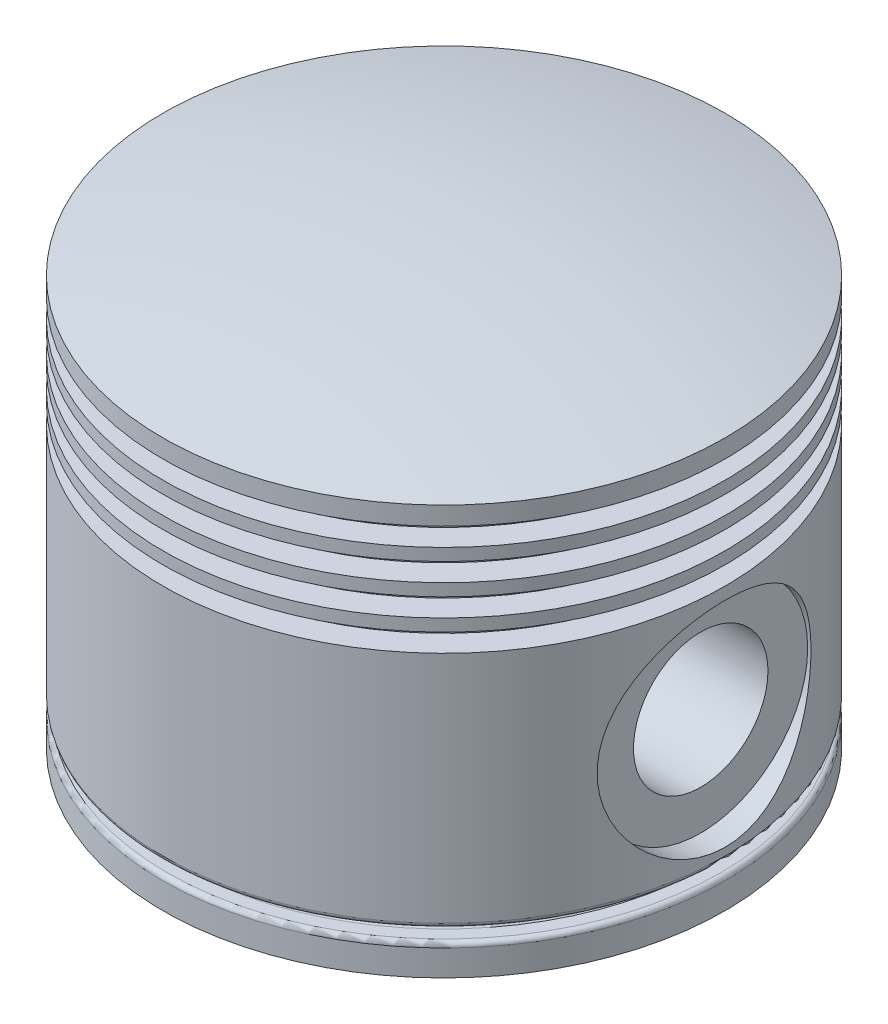
SolidWorks part; units mm, degrees
ref_plane "Front Plane" through (0, 0, 0) normal (0, 0, 1) x (1, 0, 0)
ref_plane "Top Plane" through (0, 0, 0) normal (0, 1, 0) x (1, 0, 0)
ref_plane "Right Plane" through (0, 0, 0) normal (1, 0, 0) x (0, 0, -1)
sketch "Sketch1" plane through (0, 0, 0) normal (0, 0, 1) x (1, 0, 0)
  line L0 (0, 0) -> (0, 81299.3192) construction
  line L1 (0, 0) -> (81299.3192, 0) construction
  line L2 (0, 72.6833) -> (0, 62)
  line L3 (0, 62) -> (37, 62)
  line L4 (37, 62) -> (37, 0)
  line L9 (37, 0) -> (46, 0)
  line L10 (46, 0) -> (46, 5)
  line L11 (46, 5) -> (42.5, 5)
  line L12 (42.5, 5) -> (42.5, 7)
  line L13 (42.5, 7) -> (46, 7)
  line L18 (46, 7) -> (46, 46)
  line L19 (46, 46) -> (42, 46)
  line L20 (42, 46) -> (42, 49)
  line L21 (42, 49) -> (46, 49)
  line L22 (46, 49) -> (46, 51)
  line L23 (46, 51) -> (42, 51)
  line L24 (42, 51) -> (42, 54)
  line L25 (42, 54) -> (46, 54)
  line L26 (46, 54) -> (46, 56)
  line L27 (46, 56) -> (42, 56)
  line L28 (42, 56) -> (42, 59)
  line L29 (42, 59) -> (46, 59)
  line L30 (46, 59) -> (46, 61)
  line L31 (46, 61) -> (42, 61)
  line L32 (42, 61) -> (42, 64)
  line L33 (42, 64) -> (46, 64)
  line L34 (46, 64) -> (46, 67)
  arc A0 (46, 67) -> (0, 72.6833) centre (0, -116.3167) ccw
  dimension "D1" = 189
  dimension "D2" = 84
  dimension "D3" = 92
  dimension "D4" = 74
  dimension "D5" = 39
  dimension "D6" = 85
  dimension "D7" = 2
  dimension "D8" = 7
  dimension "D11" = 3
  dimension "D12" = 2
  dimension "D14" = 62
  dimension "D15" = 3
revolve "Revolve1" add sketch "Sketch1" angle 360 about L0
sketch "Sketch5" plane through (0, 0, 0) normal (1, 0, 0) x (0, 0, -1)
  circle A0 centre (0, 26.5) radius 19.5
  dimension "D1" = 39
  dimension "D2" = 26.5
extrude "Boss-Extrude1" add sketch "Sketch5" along normal up to next from offset 25
ref_plane "Plane1" through (46, 0, 0) normal (1, 0, 0) x (0, 0, -1)
hole_wizard "CBORE for M5 Hex Head Bolt2" positions "Sketch12" profile "Sketch11" counterbore size "M5" standard "ANSI Metric" end condition up to next
sketch "Sketch12" plane through (46, 0, 0) normal (1, 0, 0) x (0, 0, -1)
  point P0 (0, 26.5)
sketch "Sketch11" plane through (46, 26.5, 0) normal (0, 1, 0) x (0, 0, -1)
  line L0 (0, 0) -> (0, 92)
  line L1 (0, 92) -> (11, 92)
  line L3 (11, 92) -> (11, 4)
  line L4 (11, 4) -> (17.5, 4)
  line L5 (17.5, 4) -> (17.5, 0)
  line L7 (17.5, 0) -> (0, 0)
  line L11 (0, -6.35) -> (0, 107.95) construction
  dimension "Thru Hole Dia." = 22
  dimension "Thru Hole Depth" = 92
  dimension "C'Bore Dia." = 35
  dimension "C'Bore Depth" = 4
mirror "Mirror1" about plane through (0, 0, 0) normal (1, 0, 0) of "CBORE for M5 Hex Head Bolt2", "Boss-Extrude1"
fillet "Fillet1" radius 0.75 4 edges at (0, 5, -46) (0, 7, -46) (0, 5, -42.5) (0, 7, -42.5)
